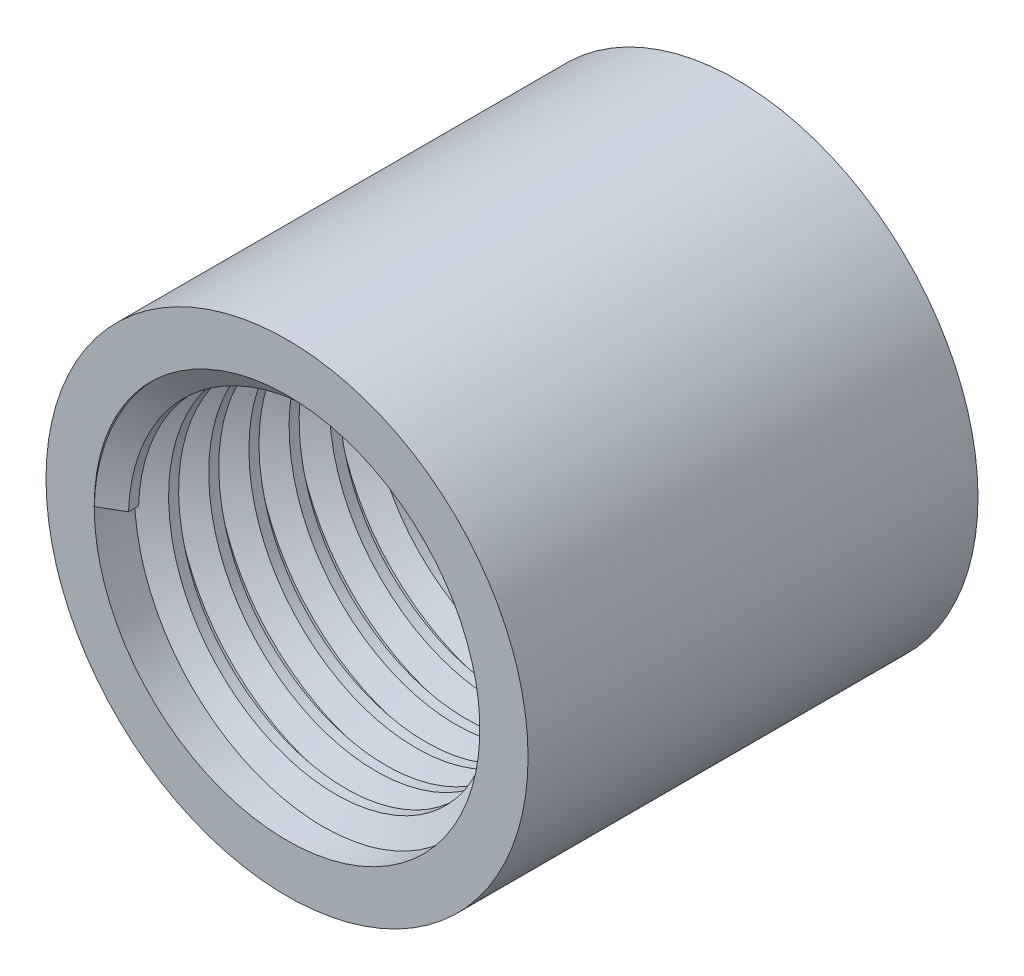
SolidWorks part; units mm, degrees
ref_plane "Front Plane" through (0, 0, 0) normal (0, 0, 1) x (1, 0, 0)
ref_plane "Top Plane" through (0, 0, 0) normal (0, 1, 0) x (1, 0, 0)
ref_plane "Right Plane" through (0, 0, 0) normal (1, 0, 0) x (0, 0, -1)
sketch "Sketch1" plane through (0, 0, 0) normal (0, 0, 1) x (1, 0, 0)
  circle A0 centre (0, 0) radius 7.5
  dimension "D1" = 15
extrude "Boss-Extrude1" add sketch "Sketch1" along normal mid plane 14
hole_wizard "Ø10.0mm Dowel Hole1" positions "3DSketch1" profile "Sketch8" hole size "Ø10.0" standard "ANSI Metric"
sketch3d "3DSketch1"
  point P0 (0, -0.0103, 7)
  point P6 (0, -0.0103, 7)
sketch "Sketch8" plane through (0, -0.0103, 7) normal (1, 0, 0) x (0, -1, 0)
  line L0 (0, 0) -> (0, 13.0043)
  line L1 (0, 13.0043) -> (5, 10)
  line L2 (5, 10) -> (5, 0)
  line L5 (5, 0) -> (0, 0)
  line L10 (0, 13.0043) -> (-5, 10) construction
  line L11 (0, -6.35) -> (0, 107.95) construction
  dimension "Hole Dia." = 10
  dimension "Hole Depth" = 10
  dimension "Drill Angle" = 118
sketch "Sketch12" plane through (0, 0, 7) normal (0, 0, 1) x (1, 0, 0)
  circle A0 centre (0, 0) radius 6
  dimension "D1" = 12
extrude "Cut-Extrude1" cut sketch "Sketch12" against normal blind 8
thread "Thread1" pitch 1.25 method extrude profile "Thread Profile3" start angle 0, offset 0, length 8, pitch 1.25, diameter 12
ref_plane "Plane3" through (-6, 0, 7) normal (0, -1, 0) x (-1, 0, 0)
sketch "Thread Profile3" plane through (-6, 0, 7) normal (0, -1, 0) x (-1, 0, 0)
  line L0 (0, 0) -> (0, 1.25) construction
  line L11 (0, 0) -> (0, 1.0937)
  line L12 (0, 1.0937) -> (-0.6766, 0.7031)
  line L13 (-0.6766, 0.7031) -> (-0.6766, 0.3906)
  line L15 (-0.6766, 0.3906) -> (0, 0)
  line L17 (-0.6766, 0.5469) -> (0, 0.5469) construction
  point P2 (0, 0)
  dimension "Pitch" = 1.25
  dimension "Profile_Angle" = 60
  dimension "Profile_Land" = 0.3125
  dimension "Profile_Height" = 0.6766
